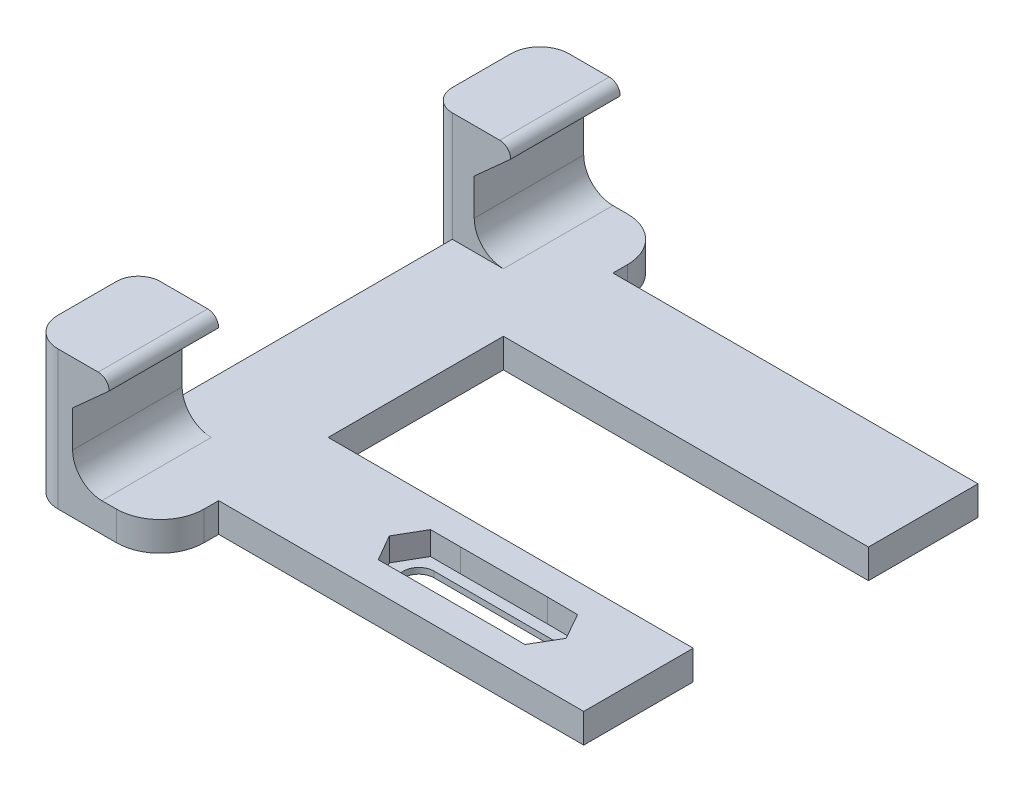
SolidWorks part; units mm, degrees
ref_plane "Plan de face" through (0, 0, 0) normal (0, 0, 1) x (1, 0, 0)
ref_plane "Plan de dessus" through (0, 0, 0) normal (0, 1, 0) x (1, 0, 0)
ref_plane "Plan de droite" through (0, 0, 0) normal (1, 0, 0) x (0, 0, -1)
sketch "Esquisse1" plane through (0, 0, 0) normal (0, 0, 1) x (1, 0, 0)
  line L0 (-31.9829, 17) -> (-31.9829, 0)
  line L1 (-31.9829, 0) -> (-16.9829, 0)
  line L2 (-16.9829, 0) -> (-16.9829, 4)
  line L3 (-16.9829, 4) -> (-24.9829, 4)
  line L4 (-28.9829, 8) -> (-28.9829, 13)
  line L5 (-28.9829, 19) -> (-29.9829, 19)
  line L6 (-31.9829, 18) -> (-31.9829, 17)
  line L7 (-28.9829, 19) -> (-25.4829, 19)
  line L10 (-29.9829, 19) -> (-31.9829, 19)
  line L11 (-31.9829, 19) -> (-31.9829, 18)
  line L12 (-28.9829, 13) -> (-23.9829, 17.5)
  arc A2 (-25.4829, 19) -> (-23.9829, 17.5) centre (-25.4829, 17.5) cw
  arc A4 (-24.9829, 4) -> (-28.9829, 8) centre (-24.9829, 8) cw
  dimension "D6" = 15
  dimension "D7" = 1.5
  dimension "D9" = 4
  dimension "D1" = 9
  dimension "D2" = 3
  dimension "D3" = 4
extrude "Boss.-Extru.1" add sketch "Esquisse1" along normal blind 70
sketch "Esquisse5" plane through (-31.9829, 0, 0) normal (-1, 0, 0) x (0, 0, 1)
  line L0 (0, 19) -> (0, 0) construction
  line L1 (15, 19) -> (55, 19)
  line L2 (15, 19) -> (15, 4)
  line L3 (15, 4) -> (55, 4)
  line L4 (55, 19) -> (55, 4)
  line L6 (70, 0) -> (0, 0) construction
  line L7 (70, 19) -> (0, 19) construction
  dimension "D1" = 15
  dimension "D2" = 40
  dimension "D3" = 4
  dimension "D4" = 0
extrude "Enlèv. mat.-Extru.2" cut sketch "Esquisse5" against normal blind 10
sketch "Esquisse7" plane through (-16.9829, 0, 0) normal (1, 0, 0) x (0, 0, -1)
  line L0 (-70, 0) -> (-70, 4) construction
  line L15 (-70, 0) -> (0, 0) construction
  line L29 (-70, 4) -> (0, 4) construction
  line L38 (-23, 4) -> (-8, 4)
  line L39 (-23, 4) -> (-23, 0)
  line L40 (-23, 0) -> (-8, 0)
  line L41 (-8, 4) -> (-8, 0)
  line L42 (0, 0) -> (0, 4) construction
  line L44 (-62, 4) -> (-47, 4)
  line L45 (-62, 4) -> (-62, 0)
  line L46 (-62, 0) -> (-47, 0)
  line L47 (-47, 4) -> (-47, 0)
  point P14 (-70, 2)
  point P15 (-47, 2)
  dimension "D1" = 15
  dimension "D2" = 8
  dimension "D3" = 8
  dimension "D4" = 15
extrude "Boss.-Extru.4" add sketch "Esquisse7" along normal blind 50
sketch "Esquisse17" plane through (0, 4, 0) normal (0, 1, 0) x (1, 0, 0)
  line L1 (23.1449, -54.5367) -> (21.1128, -50.9435)
  line L2 (21.1128, -50.9435) -> (16.9849, -50.9068)
  line L3 (16.9849, -50.9068) -> (14.8892, -54.4633)
  line L4 (14.8892, -54.4633) -> (16.9213, -58.0565)
  line L5 (16.9213, -58.0565) -> (21.0492, -58.0932)
  line L6 (21.0492, -58.0932) -> (23.1449, -54.5367)
  line L7 (-1.111, -54.5) -> (0.953, -58.075)
  line L8 (0.953, -58.075) -> (5.0811, -58.075)
  line L9 (5.0811, -58.075) -> (7.1451, -54.5)
  line L10 (7.1451, -54.5) -> (5.0811, -50.925)
  line L11 (5.0811, -50.925) -> (0.953, -50.925)
  line L12 (0.953, -50.925) -> (-1.111, -54.5)
  line L13 (5.0811, -50.925) -> (16.9849, -50.9068)
  line L14 (16.9213, -58.0565) -> (5.0811, -58.075)
  line L15 (17.0171, -54.5) -> (4.3869, -54.5) construction
  line L17 (33.0171, -47) -> (33.0171, -62) construction
  line L18 (14.7984, -47) -> (14.7984, -62) construction
  line L19 (33.0171, -47) -> (-16.9829, -47) construction
  line L20 (33.0171, -62) -> (-16.9829, -62) construction
  circle A0 centre (19.0171, -54.5) radius 3.575 construction
  circle A1 centre (3.0171, -54.5) radius 3.575 construction
  dimension "D1" = 7.15
  dimension "D2" = 14
  dimension "D3" = 16
extrude "Enlèv. mat.-Extru.6" cut sketch "Esquisse17" against normal blind 3.2 contours L11 L12 L7 L8 L9 L10 | L14 L4 L3 L13 L10 L9 | L5 L6 L1 L2 L3 L4
sketch "Esquisse18" plane through (0, 0.8, 0) normal (0, 1, 0) x (1, 0, 0)
  line L0 (-1.111, -54.5) -> (23.1449, -54.5367) construction
  line L1 (2.929, -52.4061) -> (19.1049, -52.4306)
  line L3 (19.1049, -56.6306) -> (2.929, -56.6061)
  circle A0 centre (2.929, -54.5061) radius 2.1
  circle A1 centre (19.1049, -54.5306) radius 2.1
  dimension "D1" = 4.2
  dimension "D2" = 4.04
  dimension "D3" = 4.04
extrude "Enlèv. mat.-Extru.7" cut sketch "Esquisse18" against normal blind 3.2 contours A0 L0 L1 | L0 A0 | A0 L0 A1 L1 | L0 A0 L3 A1 | L0 A1 L3 | A1 L0
fillet "Congé1" radius 6 2 edges at (-16.9829, 2, 70) (-16.9829, 2, 0)
sketch "Esquisse19" plane through (0, 0, 0) normal (0, -1, 0) x (1, 0, 0)
  line L6 (-16.9829, 35) -> (-52.1975, 35) construction
  line L7 (-31.9829, 70) -> (-34.9829, 70)
  line L8 (-31.9829, 70) -> (-31.9829, 55)
  line L9 (-31.9829, 55) -> (-34.9829, 55)
  line L10 (-34.9829, 70) -> (-34.9829, 55)
  line L11 (-16.9829, 47) -> (-16.9829, 23) construction
  line L12 (-31.9829, 15) -> (-34.9829, 15)
  line L13 (-34.9829, 0) -> (-34.9829, 15)
  line L14 (-31.9829, 0) -> (-34.9829, 0)
  line L15 (-31.9829, 0) -> (-31.9829, 15)
  dimension "D1" = 15
  dimension "D2" = 3
extrude "Boss.-Extru.6" add sketch "Esquisse19" against normal blind 19
fillet "Congé3" radius 4 2 edges at (-34.9829, 9.5, 70) (-34.9829, 9.5, 0)
fillet "Congé5" radius 3 2 edges at (-34.9829, 9.5, 55) (-34.9829, 9.5, 15)
